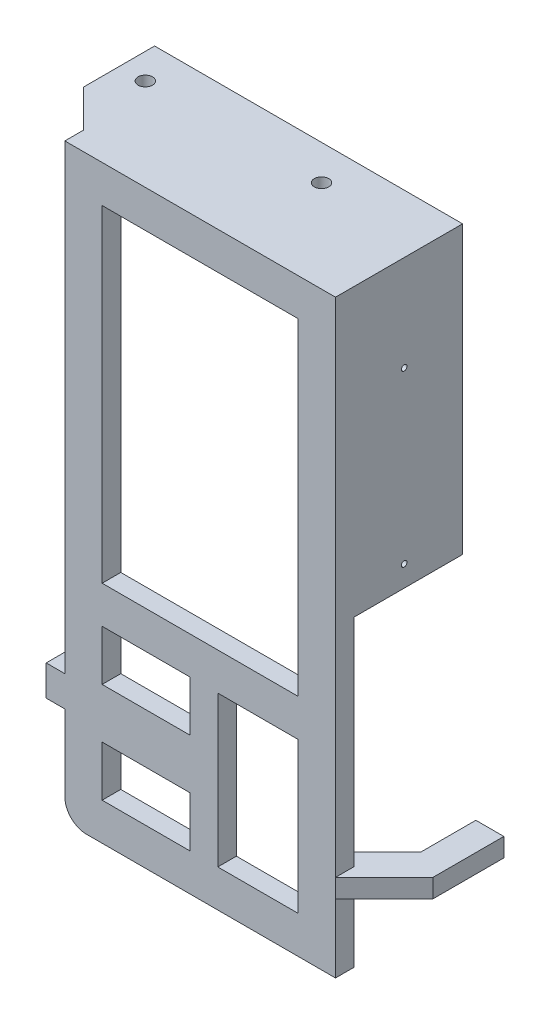
SolidWorks part; units mm, degrees
ref_plane "前视基准面" through (0, 0, 0) normal (0, 0, 1) x (1, 0, 0)
ref_plane "上视基准面" through (0, 0, 0) normal (0, 1, 0) x (1, 0, 0)
ref_plane "右视基准面" through (0, 0, 0) normal (1, 0, 0) x (0, 0, -1)
other "Configuration Table"
sketch "草图2" plane through (-16.4, 0, 0) normal (-1, 0, 0) x (0, 0, 1)
  line L0 (-11.22, 15.6) -> (0, 15.6) construction
  line L2 (-11.22, 15.6) -> (0, 15.6)
  line L4 (0, 9.05) -> (-4, 9.05) construction
  line L8 (0, 9.05) -> (-6.55, 9.05)
  line L9 (0, 15.6) -> (4, 15.6)
  line L13 (-6.55, 9.05) -> (-6.55, 15.6)
  line L14 (-6.55, 15.6) -> (0, 9.05)
  circle A0 centre (-3.275, 12.325) radius 1.32
  point P4 (0, 0)
  point P6 (0, 0)
  point P8 (0, 0)
  line M33 (-4, 9.05) -> (0, 9.05)
  line M34 (0, 9.05) -> (0, 27.55)
  dimension "D2" = 2.64
  dimension "D1" = 45
extrude "凸台-拉伸2" add sketch "草图2" along normal blind 4 separate body contours L9 | A0 L14 L13 L8 M33 | A0 L14 L2 M34 region at (-16.4, 11.1316, -4.4684) region at (-16.4, 13.5184, -2.0816)
sketch "草图4" plane through (37.65, 0, 0) normal (1, 0, 0) x (0, 0, -1)
  line L0 (23.255, 107.6634) -> (23.255, 53.1366) construction
  line L1 (7.255, 53.1366) -> (23.255, 53.1366) construction
  line L2 (19.8734, 110.55) -> (11.6366, 110.55)
  line L3 (23.255, 110.55) -> (0, 110.55)
  line L4 (0, 53.1366) -> (23.255, 53.1366)
  line L5 (0, 110.55) -> (0, 53.1366)
  line L6 (23.255, 110.55) -> (23.255, 53.1366)
  line L8 (0, -7.25) -> (0, 31.75) construction
  circle A0 centre (10.735, 94.05) radius 0.6
  circle A1 centre (10.735, 57.65) radius 0.6
  point P12 (29.0378, 110.55)
  dimension "D2" = 1.2
  dimension "D1" = 1
extrude "凸台-拉伸5" add sketch "草图4" along normal blind 4 separate body
sketch "草图5" plane through (0, 110.55, 0) normal (0, 1, 0) x (1, 0, 0)
  line L1 (41.65, 0) -> (37.65, 0) construction
  line L2 (41.65, 23.255) -> (-24.4, 23.255)
  line L3 (41.65, 23.255) -> (41.65, 0)
  line L4 (41.65, 0) -> (-24.4, 0)
  line L5 (-24.4, 23.255) -> (-24.4, 0)
  circle A0 centre (-18.9, 15.755) radius 1.55
  circle A1 centre (18.9, 15.755) radius 1.55
  dimension "D2" = 3.1
  dimension "D1" = 5.5
extrude "凸台-拉伸6" add sketch "草图5" along normal blind 4
sketch "草图6" plane through (0, 2.7903, 0) normal (0, 1, 0) x (1, 0, 0)
  line L0 (52.0958, 21.655) -> (52.0958, 0)
  line L1 (-24.4, 0) -> (41.65, 0) construction
  line L7 (50.7958, 9.855) -> (50.7958, 15.105)
  line L8 (50.7958, 15.105) -> (49.2557, 15.105)
  line L9 (49.2557, 16.405) -> (50.7958, 16.405)
  line L10 (50.7958, 16.405) -> (50.7958, 21.655)
  line L11 (50.7958, 21.655) -> (46.0958, 21.655)
  line L12 (46.0958, 21.655) -> (46.0958, 9.855)
  line L13 (46.0958, 9.855) -> (50.7958, 9.855)
  line L18 (52.0958, 21.655) -> (46.0958, 21.655)
  line L19 (46.0958, 21.655) -> (46.0958, 0)
  line L20 (46.0958, 0) -> (52.0958, 0)
  arc A1 (49.2557, 16.405) -> (49.2557, 15.105) centre (48.4958, 15.755) ccw
  point P4 (52.4627, 9.855)
  point P7 (52.5563, 21.655)
  point P10 (0, 0)
  point P11 (52.5106, 9.869)
  dimension "D2" = 6
  dimension "D1" = 0
extrude "凸台-拉伸7" [suppressed] add sketch "草图6" along normal blind 4 separate body
sketch "草图7" plane through (0, 0, 0) normal (0, 0, 1) x (1, 0, 0)
  line L6 (-11.75, -11.9) -> (11.75, -11.9) construction
  line L7 (-24.4, 114.55) -> (41.65, 114.55)
  line L8 (-24.4, 114.55) -> (-24.4, -11.9)
  line L9 (-24.4, -11.9) -> (41.65, -11.9)
  line L10 (41.65, 114.55) -> (41.65, -11.9)
  line L13 (41.65, 114.55) -> (41.65, 53.1366) construction
extrude "凸台-拉伸8" add sketch "草图7" along normal blind 4
sketch "草图11" plane through (0, 0, 0) normal (0, 0, -1) x (-1, 0, 0)
  line L0 (-33.65, -3.9) -> (-33.65, 110.55)
  line L1 (-33.65, -3.9) -> (8.4, -3.9)
  line L3 (8.4, -3.9) -> (8.4, 110.55)
  line L4 (-37.65, 110.55) -> (24.4, 110.55) construction
  line L5 (24.4, -11.9) -> (-41.65, -11.9) construction
  line L6 (16.4, -7.25) -> (16.4, 21.75) construction
  line L7 (-10.4, -3.9) -> (-10.4, 28.4)
  line L8 (-10.4, 28.4) -> (8.4, 28.4)
  line L9 (8.4, 28.4) -> (8.4, 36.4)
  line L10 (8.4, 36.4) -> (-16.4, 36.4)
  line L11 (-16.4, 36.4) -> (-16.4, -3.9)
  line L12 (-16.4, 21.75) -> (-16.4, 7.7903) construction
  line L13 (11.32, 36.4) -> (-11.32, 36.4) construction
  line L14 (8.4, 6.9) -> (-10.4, 6.9)
  line L15 (-10.4, 17.6) -> (8.4, 17.6)
  line L16 (9.52, 15.6) -> (-9.52, 15.6) construction
  line L17 (-11.32, 8.9) -> (11.32, 8.9) construction
  line L18 (-16.4, 2.7903) -> (-16.4, -7.25) construction
  line L19 (-10.73, -11.9) -> (10.73, -11.9) construction
  line L20 (-16.4, 2.7903) -> (-16.4, -7.25)
  line L21 (-11.75, -11.9) -> (11.75, -11.9)
  line L22 (16.4, -7.25) -> (16.4, 31.75)
  line L23 (8.4, 36.4) -> (11.75, 36.4)
  line L24 (16.4, 31.75) -> (16.4, 110.55)
  line L25 (24.4, 110.55) -> (-37.65, 110.55) construction
  line L26 (8.4, 110.55) -> (24.4, 110.55)
  line L27 (24.4, 110.55) -> (24.4, -11.9) construction
  line L28 (24.4, 110.55) -> (24.4, -11.9)
  line L29 (24.4, -11.9) -> (-41.65, -11.9)
  line L30 (-33.65, 110.55) -> (24.4, 110.55)
  line L31 (-41.65, -11.9) -> (-41.65, 53.1366) construction
  line L32 (24.4, 106.55) -> (-33.65, 106.55)
  line L33 (-41.65, 114.55) -> (24.4, 114.55) construction
  line L34 (-10.4, 28.4) -> (-33.65, 28.4)
  line L35 (-16.4, 36.4) -> (-33.65, 36.4)
  arc A0 (16.4, 31.75) -> (11.75, 36.4) centre (11.75, 31.75) ccw construction
  arc A1 (-16.4, -7.25) -> (-11.75, -11.9) centre (-11.75, -7.25) ccw construction
  arc A2 (11.75, -11.9) -> (16.4, -7.25) centre (11.75, -7.25) ccw construction
  arc A3 (16.4, 31.75) -> (11.75, 36.4) centre (11.75, 31.75) ccw
  arc A4 (-16.4, -7.25) -> (-11.75, -11.9) centre (-11.75, -7.25) ccw
  arc A5 (11.75, -11.9) -> (16.4, -7.25) centre (11.75, -7.25) ccw
  point P51 (-16.4, 28.4)
  point P54 (0, 0)
  line M8 (-41.65, -11.9) -> (24.4, -11.9)
  line M9 (24.4, -11.9) -> (24.4, 110.55)
  line M12 (20.4, 9.05) -> (16.4, 9.05)
  line M14 (16.4, 15.6) -> (20.4, 15.6)
  line M15 (20.4, 15.6) -> (20.4, 9.05)
  dimension "D1" = 8
  dimension "D2" = 8
  dimension "D3" = 8
  dimension "D4" = 6
  dimension "D5" = 2
  dimension "D6" = 2
  dimension "D7" = 8
  dimension "D8" = 8
extrude "切除-拉伸3" cut sketch "草图11" against normal through all contours L3 L32 L0 L1 L11 L10 | L7 L15 L3 L8 | L3 L14 L7 L1 | A5 L32 L24 L22 M8 M9 M14 M15 M12 | L11 L34 L0 L1 region at (25.025, 12.25, 0) region at (12.625, 71.475, 0) region at (1, 1.5, 0) region at (1, 23, 0) region at (-20.4313, 48.0237, 0)
sketch "草图12" plane through (0, 2.7903, 0) normal (0, 1, 0) x (1, 0, 0)
  line L0 (52.0958, 21.655) -> (52.0958, 9.855)
  line L1 (46.0958, 9.855) -> (36.2408, 0)
  line L2 (-11.75, 0) -> (41.65, 0) construction
  line L3 (52.0958, 9.855) -> (52.0958, 6.4458)
  line L5 (52.0958, 6.4458) -> (41.65, -4)
  line L6 (36.2408, 0) -> (41.65, -4)
  line L7 (50.7958, 9.855) -> (50.7958, 15.105)
  line L8 (50.7958, 15.105) -> (49.2557, 15.105)
  line L9 (49.2557, 16.405) -> (50.7958, 16.405)
  line L10 (50.7958, 16.405) -> (50.7958, 21.655)
  line L11 (50.7958, 21.655) -> (46.0958, 21.655)
  line L12 (46.0958, 21.655) -> (46.0958, 9.855)
  line L13 (46.0958, 9.855) -> (50.7958, 9.855)
  line L18 (52.0958, 21.655) -> (46.0958, 21.655)
  line L19 (46.0958, 21.655) -> (46.0958, 9.855)
  line L20 (46.0958, 9.855) -> (52.0958, 9.855)
  arc A1 (49.2557, 16.405) -> (49.2557, 15.105) centre (48.4958, 15.755) ccw
  line M13 (50.7958, 9.855) -> (50.7958, 15.105)
  line M14 (50.7958, 15.105) -> (49.2557, 15.105)
  arc M15 (49.2557, 15.105) -> (49.2557, 16.405) centre (48.4958, 15.755) cw
  line M16 (49.2557, 16.405) -> (50.7958, 16.405)
  line M17 (50.7958, 16.405) -> (50.7958, 21.655)
  line M18 (50.7958, 21.655) -> (46.0958, 21.655)
  line M19 (46.0958, 21.655) -> (46.0958, 9.855)
  line M20 (46.0958, 9.855) -> (50.7958, 9.855)
  dimension "D2" = 6
  dimension "D3" = 45
  dimension "D1" = 0
extrude "凸台-拉伸9" add sketch "草图12" along normal blind 4 contours M20 M13 M14 M15 M16 M17 M18 M19 | L20 L1 L6 L5 L3 M20 | L20 L0 L18 M13 M17 M16 M15 M14 region at (50.8703, 2.7903, -15.755) region at (44.6332, 2.7903, -3.6048) region at (50.6687, 2.7903, -19.03)
sketch "草图13" plane through (0, 110.55, 0) normal (0, -1, 0) x (1, 0, 0)
  line L0 (-24.4, -8) -> (-16.4, 0)
  line L1 (-24.4, -23.255) -> (-24.4, 0) construction
  line L4 (-16.4, 4) -> (-16.4, 0) construction
  line L5 (-16.4, 4) -> (-16.4, 0)
  line L6 (-16.4, 4) -> (-24.4, 4)
  line L7 (-24.4, 4) -> (-24.4, -8)
  point P1 (-24.4, -7.9682)
  dimension "D1" = 45
extrude "切除-拉伸4" cut sketch "草图13" against normal mid plane 20
